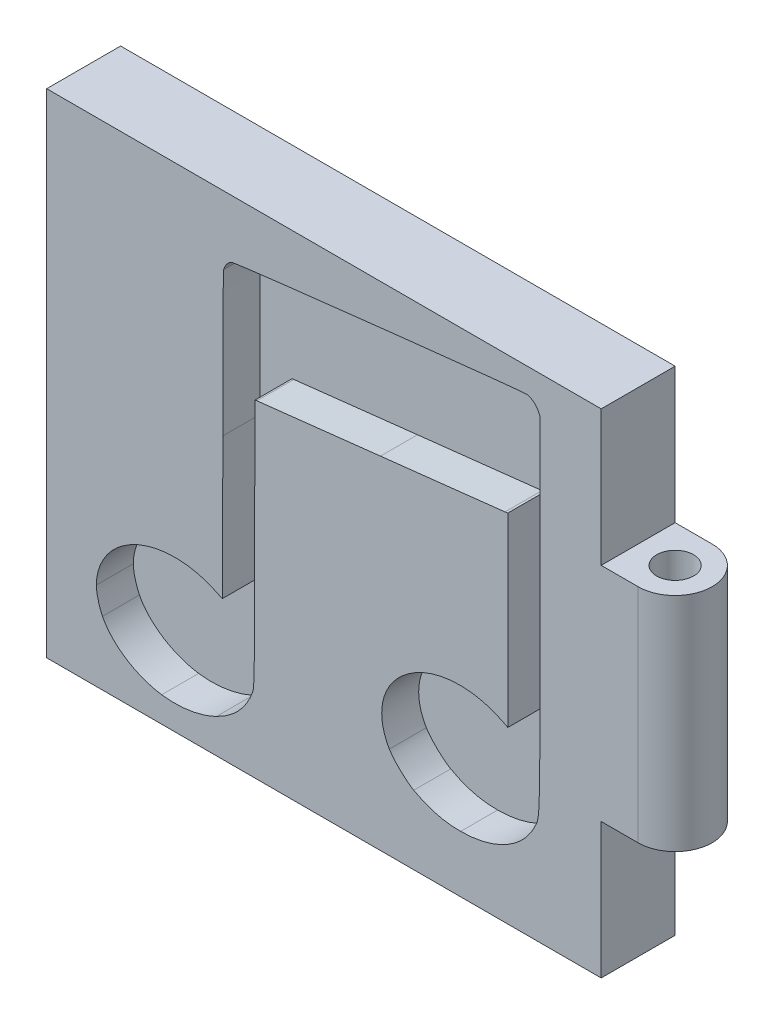
SolidWorks part; units mm, degrees
ref_plane "Alzado" through (0, 0, 0) normal (0, 0, 1) x (1, 0, 0)
ref_plane "Planta" through (0, 0, 0) normal (0, 1, 0) x (1, 0, 0)
ref_plane "Vista lateral" through (0, 0, 0) normal (1, 0, 0) x (0, 0, -1)
sketch "Croquis1" plane through (0, 0, 0) normal (0, 1, 0) x (1, 0, 0)
  line L1 (-11.25, -1.5) -> (11.25, -1.5)
  line L2 (-11.25, -1.5) -> (-11.25, 1.5)
  line L3 (-11.25, 1.5) -> (11.25, 1.5)
  line L4 (11.25, -1.5) -> (11.25, 1.5)
  line L5 (-11.25, -1.5) -> (11.25, 1.5) construction
  line L6 (-11.25, 1.5) -> (11.25, -1.5) construction
  point P0 (0, 0)
  dimension "D1" = 3
  dimension "D2" = 22.5
extrude "Saliente-Extruir1" add sketch "Croquis1" along normal blind 20
ref_plane "Plano1" through (0, 10, 0) normal (0, 1, 0) x (1, 0, 0)
sketch "Croquis3" plane through (0, 10, 0) normal (0, 1, 0) x (1, 0, 0)
  line L0 (11.25, 1.5) -> (14.25, -1.5) construction
  line L1 (11.25, 1.5) -> (14.25, 1.5) construction
  line L2 (11.25, 1.5) -> (11.25, -1.5)
  line L3 (11.25, -1.5) -> (14.25, -1.5) construction
  line L4 (14.25, 1.5) -> (14.25, -1.5) construction
  line L5 (11.25, 1.5) -> (12.75, 1.5)
  line L6 (11.25, -1.5) -> (12.75, -1.5)
  arc A0 (12.75, -1.5) -> (12.75, 1.5) centre (12.75, 0) ccw
  circle A1 centre (12.75, 0) radius 0.75
  dimension "D2" = 1.5
  dimension "D1" = 3
extrude "Saliente-Extruir2" add sketch "Croquis3" along normal blind 4.5 and the other way blind 4.5
sketch "Sketch1" plane through (0, 0, 1.5) normal (0, 0, 1) x (1, 0, 0)
  line L0 (8.6891, 18.657) -> (8.7637, 18.5028)
  line L1 (8.7637, 18.5028) -> (8.763, 11.5895)
  line L2 (7.2534, 7.0158) -> (7.4628, 6.91)
  line L3 (7.4628, 6.91) -> (7.4628, 10.6779)
  line L4 (7.4628, 10.6779) -> (7.4628, 14.4457)
  line L5 (7.4628, 14.4457) -> (7.3485, 14.4268)
  line L6 (-2.7233, 13.2973) -> (-2.8016, 13.2802)
  line L7 (-2.8016, 13.2802) -> (-2.8113, 8.2391)
  spline S0 degree 3 poles (-6.5826, 1.0375) (-7.6253, 1.1879) (-8.5953, 1.8153) (-8.9861, 2.5922) knots 0 0 0 0 1 1 1 1
  spline S1 degree 3 poles (-8.9861, 2.5922) (-9.1237, 2.8657) (-9.2371, 3.3064) (-9.2363, 3.5644) knots 0 0 0 0 1 1 1 1
  spline S2 degree 3 poles (-9.2363, 3.5644) (-9.2347, 4.0952) (-9.0022, 4.6562) (-8.6053, 5.0875) knots 0 0 0 0 1 1 1 1
  spline S3 degree 3 poles (-8.6053, 5.0875) (-7.6013, 6.1782) (-5.7458, 6.4579) (-4.3182, 5.7337) knots 0 0 0 0 1 1 1 1
  spline S4 degree 3 poles (-4.3182, 5.7337) (-4.221, 5.6844) (-4.133, 5.644) (-4.1227, 5.644) knots 0 0 0 0 1 1 1 1
  spline S5 degree 3 poles (-4.1227, 5.644) (-4.1124, 5.644) (-4.1039, 8.2216) (-4.1038, 11.3719) knots 0 0 0 0 1 1 1 1
  spline S6 degree 3 poles (-4.1038, 11.3719) (-4.1036, 15.4042) (-4.0922, 17.1414) (-4.0652, 17.2405) knots 0 0 0 0 1 1 1 1
  spline S7 degree 3 poles (-4.0652, 17.2405) (-4.0124, 17.4338) (-3.8905, 17.5848) (-3.7295, 17.6561) knots 0 0 0 0 1 1 1 1
  spline S8 degree 3 poles (-3.7295, 17.6561) (-3.5607, 17.7309) (8.0436, 19.0339) (8.2363, 18.9997) knots 0 0 0 0 1 1 1 1
  spline S9 degree 3 poles (8.2363, 18.9997) (8.4246, 18.9662) (8.6059, 18.8291) (8.6891, 18.657) knots 0 0 0 0 1 1 1 1
  spline S10 degree 3 poles (8.763, 11.5895) (8.7623, 3.8855) (8.7797, 4.4217) (8.5134, 3.892) knots 0 0 0 0 1 1 1 1
  spline S11 degree 3 poles (8.5134, 3.892) (8.0267, 2.9239) (6.8647, 2.3006) (5.5467, 2.3006) knots 0 0 0 0 1 1 1 1
  spline S12 degree 3 poles (5.5467, 2.3006) (4.8437, 2.3006) (4.2464, 2.456) (3.6441, 2.7955) knots 0 0 0 0 1 1 1 1
  spline S13 degree 3 poles (3.6441, 2.7955) (3.3173, 2.9797) (2.8291, 3.4488) (2.6546, 3.7464) knots 0 0 0 0 1 1 1 1
  spline S14 degree 3 poles (2.6546, 3.7464) (2.1326, 4.6364) (2.277, 5.676) (3.0289, 6.4403) knots 0 0 0 0 1 1 1 1
  spline S15 degree 3 poles (3.0289, 6.4403) (4.0624, 7.4909) (5.8353, 7.7324) (7.2534, 7.0158) knots 0 0 0 0 1 1 1 1
  spline S16 degree 3 poles (7.3485, 14.4268) (7.2857, 14.4163) (5.0114, 14.1618) (2.2946, 13.861) knots 0 0 0 0 1 1 1 1
  spline S17 degree 3 poles (2.2946, 13.861) (-0.4221, 13.5603) (-2.6802, 13.3066) (-2.7233, 13.2973) knots 0 0 0 0 1 1 1 1
  spline S18 degree 3 poles (-2.8113, 8.2391) (-2.8205, 3.4336) (-2.824, 3.189) (-2.8864, 3.0045) knots 0 0 0 0 1 1 1 1
  spline S19 degree 3 poles (-2.8864, 3.0045) (-3.1293, 2.2848) (-3.6179, 1.7486) (-4.3622, 1.3852) knots 0 0 0 0 1 1 1 1
  spline S20 degree 3 poles (-4.3622, 1.3852) (-5.0343, 1.057) (-5.8416, 0.9306) (-6.5826, 1.0375) knots 0 0 0 0 1 1 1 1
  point P0 (0, 0)
extrude "Cortar-Extruir2" cut sketch "Sketch1" against normal blind 1.5
